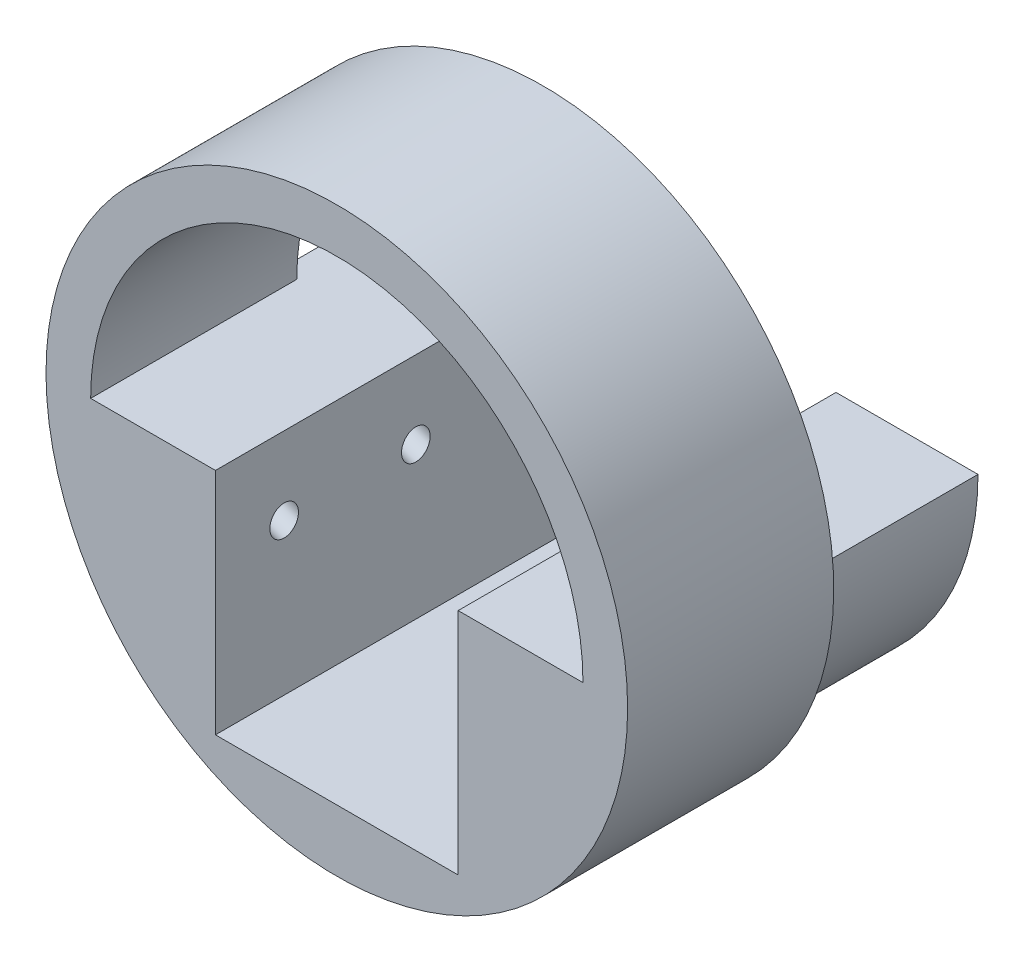
SolidWorks part; units mm, degrees
material "6061-T6 (SS)"
ref_plane "Front Plane" through (0, 0, 0) normal (0, 0, 1) x (1, 0, 0)
ref_plane "Top Plane" through (0, 0, 0) normal (0, 1, 0) x (1, 0, 0)
ref_plane "Right Plane" through (0, 0, 0) normal (1, 0, 0) x (0, 0, -1)
sketch "Sketch1" plane through (0, 0, 0) normal (0, 0, 1) x (1, 0, 0)
  circle A0 centre (0, 0) radius 25.4
  dimension "D1" = 50.8
extrude "Boss-Extrude1" add sketch "Sketch1" along normal blind 33
ref_axis "Optic axis" through (0, 0, -1) along (0, 0, 1)
sketch "Sketch2" plane through (0, 0, 33) normal (0, 0, 1) x (1, 0, 0)
  line L0 (-17.1244, 0) -> (18.5365, 0) construction
  line L1 (-10.6, 6.5644) -> (-10.6, -20.2339) construction
  line L2 (-8.6223, -20) -> (11.4163, -20) construction
  line L3 (10.6, 5.5129) -> (10.6, -20) construction
  line L4 (-21.5, 0) -> (-10.6, 0)
  line L5 (-10.6, 0) -> (-10.6, -20)
  line L6 (-10.6, -20) -> (10.6, -20)
  line L7 (10.6, -20) -> (10.6, 0)
  line L8 (10.6, 0) -> (21.5, 0)
  arc A2 (21.5, 0) -> (-21.5, 0) centre (0, 0) ccw
  dimension "D1" = 10.6
  dimension "D2" = 20
  dimension "D4" = 10.6
extrude "Cut-Extrude1" cut sketch "Sketch2" against normal through all
sketch "Sketch3" plane through (0, 0, 0) normal (0, 0, -1) x (-1, 0, 0)
  circle A0 centre (0, 0) radius 23
  circle A1 centre (0, 0) radius 25.4 construction
  circle A2 centre (0, 0) radius 25.4
  dimension "D1" = 46
extrude "Cut-Extrude2" cut sketch "Sketch3" against normal blind 15
ref_plane "Plane1" through (-23.8682, 8.6873, 0) normal (-0.9397, 0.342, 0) x (0, 0, -1)
hole_wizard "M3x0.5 Tapped Hole1" positions "Sketch4" profile "Sketch5" tap size "M3x0.5" standard "ANSI Metric"
sketch "Sketch4" plane through (-23.8682, 8.6873, 0) normal (-0.9397, 0.342, 0) x (0, 0, -1)
  line L0 (-33, 25.4) -> (-33, -25.4) construction
  line L1 (0, -23) -> (0, 23) construction
  line L2 (1, 0) -> (-21, 0) construction
  point P0 (-27, 10)
  point P2 (-15.5, 10)
  point P4 (-6, 10)
  dimension "D1" = 6
  dimension "D2" = 6
  dimension "D3" = 11.5
  dimension "D4" = 10
sketch "Sketch5" plane through (-27.2884, -0.7096, 27) normal (0, 0, 1) x (-0.342, -0.9397, 0)
  line L0 (0, 0) -> (0, 25.7511)
  line L1 (0, 25.7511) -> (1.25, 25)
  line L2 (1.25, 25) -> (1.25, 0.275)
  line L3 (1.25, 0.275) -> (1.525, 0)
  line L5 (1.525, 0) -> (0, 0)
  line L6 (-1.25, 0.275) -> (-1.525, 0) construction
  line L10 (0, 25.7511) -> (-1.25, 25) construction
  line L11 (0, -6.35) -> (0, 107.95) construction
  dimension "Tap Drill Dia." = 2.5
  dimension "Tap Drill Depth" = 25
  dimension "Near C'Sink Dia." = 3.05
  dimension "Near C'Sink Angle" = 90
  dimension "Drill Angle" = 118
cosmetic thread "Hole Thread2" parameters "D1"=14, "D2"=3
cosmetic thread "Hole Thread3" parameters "D1"=14, "D2"=3
cosmetic thread "Hole Thread4" parameters "D1"=14, "D2"=3
sketch "Sketch6" plane through (0, 0, 0) normal (0, 0, -1) x (-1, 0, 0)
  line L1 (-26.2776, 0) -> (29.236, 0)
  line L2 (-26.2776, 0) -> (-26.2776, 26.4951)
  line L3 (-26.2776, 26.4951) -> (29.236, 26.4951)
  line L4 (29.236, 0) -> (29.236, 26.4951)
  line L5 (-26.2776, 0) -> (29.236, 26.4951) construction
  line L6 (-26.2776, 26.4951) -> (29.236, 0) construction
  point P4 (1.4792, 13.2476)
extrude "Cut-Extrude3" cut sketch "Sketch6" against normal up to surface (15 mm away) up to face at (0.0164, 0.0013, 15)
sketch "Sketch7" plane through (-23.8682, 8.6873, 0) normal (-0.9397, 0.342, 0) x (0, 0, -1)
  line L0 (-27, 10) -> (-5.9918, 10) construction
